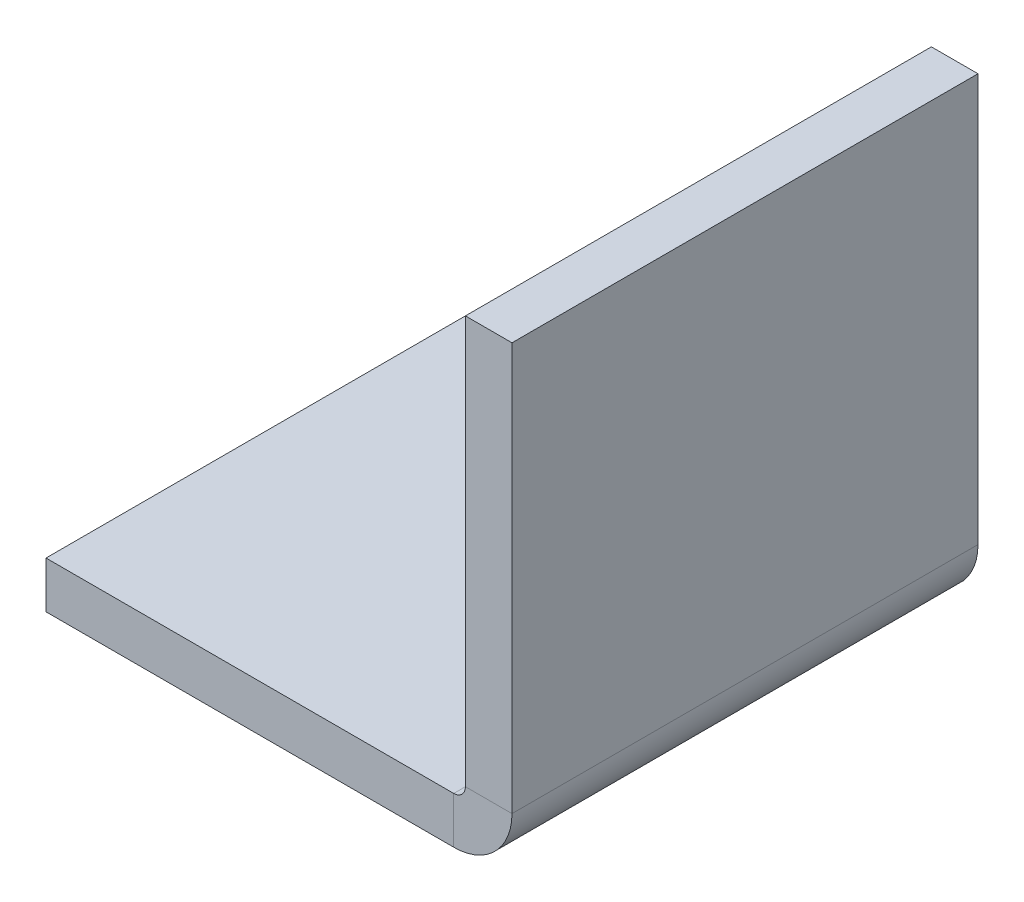
SolidWorks part; units mm, degrees
note: The reader was unsure of these and kept them because the rebuilt part matched: flange length of "Edge-Flange1".
material "ASTM A36 Steel"
ref_plane "Front Plane" through (0, 0, 0) normal (0, 0, 1) x (1, 0, 0)
ref_plane "Top Plane" through (0, 0, 0) normal (0, 1, 0) x (1, 0, 0)
ref_plane "Right Plane" through (0, 0, 0) normal (1, 0, 0) x (0, 0, -1)
sketch "Sketch1" plane through (0, 0, 0) normal (0, 1, 0) x (1, 0, 0)
  line L1 (-20, 20) -> (20, 20)
  line L2 (-20, 20) -> (-20, -20)
  line L3 (-20, -20) -> (20, -20)
  line L4 (20, 20) -> (20, -20)
  line L5 (-20, 20) -> (20, -20) construction
  line L6 (-20, -20) -> (20, 20) construction
  point P0 (0, 0)
  dimension "D1" = 40
  dimension "D2" = 40
base flange "Base-Flange1" sketch "Sketch1" thickness 4 reverse thickness direction no parameters "D1"=2
edge flange "Edge-Flange1" sketch "Sketch8" flange angle 90 flange length 40 flange position material inside bend radius 1 thickness 4 relief rectangular parameters "D6"=10
sketch "Sketch8" plane through (20, 0, 0) normal (-1, 0, 0) x (0, 0, 1)
  line L2 (-20, 0) -> (-20, 36)
  line L3 (-20, 36) -> (20, 36)
  line L4 (20, 36) -> (20, 0)
  line L5 (20, 0) -> (-20, 0) construction
  line L6 (20, 0) -> (-20, 0)
bend "EdgeBend1" bend radius 1 bend angle 90 parameters "D5"=1
sketch "Bend-Lines1" [suppressed] plane through (0, 0, 0) normal (0, 1, 0) x (1, 0, 0)
sketch "Bounding-Box1" [suppressed] plane through (0, 0, 0) normal (0, 1, 0) x (1, 0, 0)
sheet metal parameters "Sheet-Metal2" thickness 4 parameters "D1"=2
flat pattern "Flat-Pattern2" [suppressed]
sketch "Bend-Lines2" plane through (0, 0, 0) normal (0, 1, 0) x (1, 0, 0)
sketch3d "Bounding-Box2" [suppressed]
  line L0 (20, 20, 0) -> (20, -20, 0) construction
  line L1 (-20, 20, 0) -> (-20, -20, 0) construction
  line L2 (20, 20, 0) -> (-20, 20, 0) construction
  line L3 (20, -20, 0) -> (-20, -20, 0) construction
sheet metal parameters "Sheet-Metal3" thickness 4 parameters "D1"=2
flat pattern "Flat-Pattern2"
sketch "Bend-Lines2" plane through (0, 0, 0) normal (0, 1, 0) x (1, 0, 0)
  line L0 (17.042, -20) -> (17.042, 20) construction
  line L1 (17.042, -20) -> (17.042, 20) construction
sketch3d "Bounding-Box2" [suppressed]
  line L0 (54.0841, -20, 0) -> (-20, -20, 0) construction
  line L1 (54.0841, 20, 0) -> (-20, 20, 0) construction
  line L2 (54.0841, -20, 0) -> (54.0841, 20, 0) construction
  line L3 (-20, -20, 0) -> (-20, 20, 0) construction
bend of the flat pattern "Flatten-<EdgeBend1>1"
